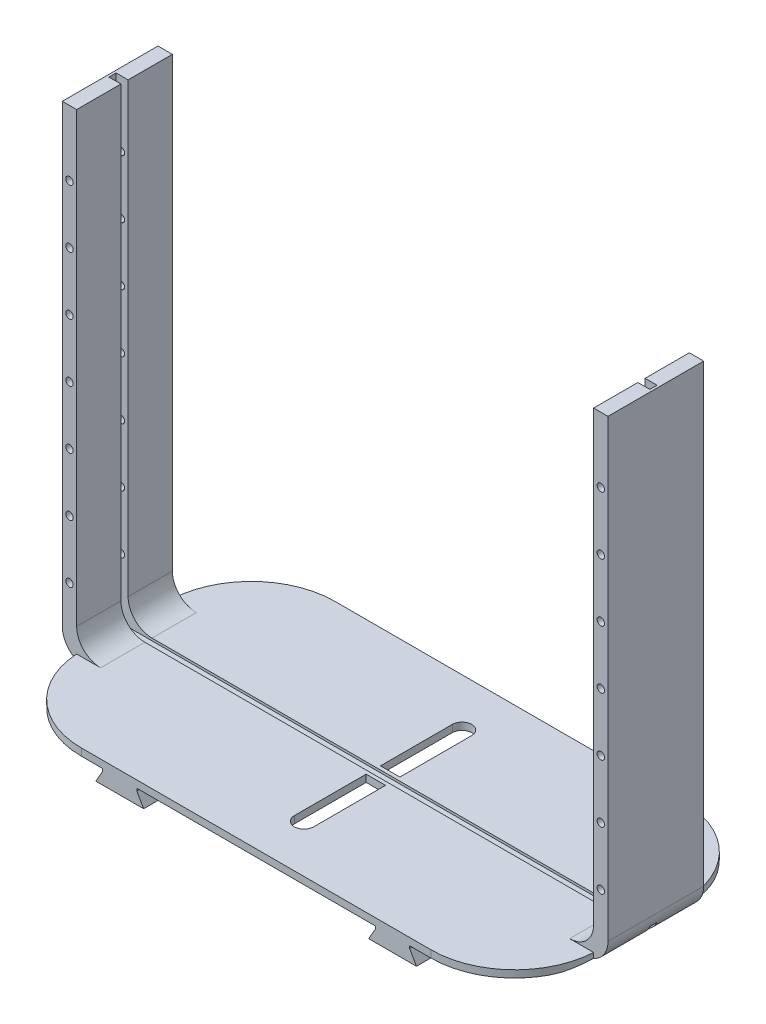
SolidWorks part; units mm, degrees
ref_plane "Front Plane" through (0, 0, 0) normal (0, 0, 1) x (1, 0, 0)
ref_plane "Top Plane" through (0, 0, 0) normal (0, 1, 0) x (1, 0, 0)
ref_plane "Right Plane" through (0, 0, 0) normal (1, 0, 0) x (0, 0, -1)
sketch "Sketch1" plane through (0, 0, 0) normal (0, 0, 1) x (1, 0, 0)
  line L0 (0, 3) -> (228, 3)
  line L1 (0, 0) -> (228, 0)
  line L2 (0, 0) -> (0, 200)
  line L3 (0, 200) -> (228, 200)
  line L4 (228, 0) -> (228, 200)
  line L5 (0, 200) -> (6, 200)
  line L6 (0, 200) -> (0, 0)
  line L7 (0, 0) -> (6, 0)
  line L8 (6, 200) -> (6, 0)
  line L9 (228, 200) -> (222, 200)
  line L10 (228, 200) -> (228, 0)
  line L11 (228, 0) -> (222, 0)
  line L12 (222, 200) -> (222, 0)
  line L13 (49.8868, 0) -> (49.8868, -1)
  line L14 (49.8868, -1) -> (47, -6)
  line L15 (47, -6) -> (67, -6)
  line L16 (67, -6) -> (64.1132, -1)
  line L17 (64.1132, -1) -> (64.1132, 0)
  line L18 (64.1132, 0) -> (49.8868, 0)
  line L19 (114, 3) -> (0, 3) construction
  line L20 (114, 200) -> (114, -47.4765) construction
  line L21 (0, 100) -> (228, 100) construction
  line L22 (57, 3) -> (57, 0) construction
  line L23 (57, -6) -> (57, 0) construction
  line L24 (163.8868, -1) -> (163.8868, 0)
  line L25 (0, 200) -> (6, 200) construction
  line L26 (0, 200) -> (6, 200) construction
  line L27 (0, 200) -> (6, 200) construction
  line L28 (3, 200) -> (3, 0) construction
  line L29 (161, -6) -> (163.8868, -1)
  line L30 (181, -6) -> (161, -6)
  line L31 (178.1132, -1) -> (181, -6)
  line L32 (178.1132, 0) -> (178.1132, -1)
  line L33 (163.8868, 0) -> (178.1132, 0)
  circle A0 centre (3, 75.75) radius 1.55
  circle A1 centre (3, 51.5) radius 1.55
  circle A2 centre (3, 27.25) radius 1.55
  circle A3 centre (3, 100) radius 1.55
  circle A4 centre (3, 172.75) radius 1.55
  circle A5 centre (3, 148.5) radius 1.55
  circle A6 centre (3, 124.25) radius 1.55
  circle A7 centre (225, 124.25) radius 1.55
  circle A8 centre (225, 148.5) radius 1.55
  circle A9 centre (225, 172.75) radius 1.55
  circle A10 centre (225, 75.75) radius 1.55
  circle A11 centre (225, 100) radius 1.55
  circle A12 centre (225, 51.5) radius 1.55
  circle A13 centre (225, 27.25) radius 1.55
  dimension "D12" = 3.1
  dimension "D13" = 3.1
  dimension "D14" = 3.1
  dimension "D15" = 3.1
  dimension "D17" = 24.25
  dimension "D1" = 3
  dimension "D2" = 228
  dimension "D3" = 6
  dimension "D4" = 6
  dimension "D5" = 200
  dimension "D6" = 60
  dimension "D7" = 60
  dimension "D8" = 20
  dimension "D9" = 1
  dimension "D10" = 1
  dimension "D11" = 6
  dimension "D16" = 24.25
  dimension "D18" = 24.25
  dimension "D19" = 24.25
extrude "Boss-Extrude1" add sketch "Sketch1" along normal blind 106 contours L3 L12 L0 L4 A12 A10 A9 A8 A7 A11 A13 | L32 L1 L24 L29 L30 L31 | L16 L17 L1 L13 L14 L15 | L12 L0 L8 L1 | L0 L12 L1 L4 | L8 L0 L2 L1 | L8 L3 L2 L0 A5 A0 A1 A2 A3 A4 A6 region at (3, 101.5702, 0) region at (3, 1.5, 0) region at (114, 1.5, 0) region at (225, 101.5702, 0) region at (225, 1.5, 0) region at (57, -3.1928, 0) region at (171, -3.1928, 0)
sketch "Sketch2" plane through (0, 200, 0) normal (0, 1, 0) x (1, 0, 0)
  line L0 (6, -106) -> (6, 0) construction
  line L1 (0, -106) -> (6, -106)
  line L2 (0, -106) -> (0, -73)
  line L3 (0, -73) -> (6, -73)
  line L4 (6, -106) -> (6, -73)
  line L5 (6, -106) -> (6, 0) construction
  line L6 (0, 0) -> (6, 0)
  line L7 (0, 0) -> (0, -33)
  line L8 (0, -33) -> (6, -33)
  line L9 (6, 0) -> (6, -33)
  line L10 (228, -106) -> (228, 0) construction
  line L11 (222, -106) -> (228, -106)
  line L12 (222, -106) -> (222, -73)
  line L13 (222, -73) -> (228, -73)
  line L14 (228, -106) -> (228, -73)
  line L15 (222, -106) -> (222, 0) construction
  line L16 (228, 0) -> (222, 0)
  line L17 (228, 0) -> (228, -33)
  line L18 (228, -33) -> (222, -33)
  line L19 (222, 0) -> (222, -33)
  line L20 (0, -53) -> (228, -53) construction
  line L21 (0, -106) -> (0, 0) construction
  line L22 (114, 0) -> (114, -106) construction
  line L23 (6, 0) -> (222, 0) construction
  line L24 (6, -106) -> (222, -106) construction
  line L25 (114, -86) -> (114, -20) construction
  line L26 (109.95, -86) -> (109.95, -20)
  line L27 (118.05, -86) -> (118.05, -20)
  line L28 (109.95, -53) -> (118.05, -53) construction
  line L29 (109.95, -56) -> (118.05, -56)
  line L30 (109.95, -56) -> (109.95, -50)
  line L31 (109.95, -50) -> (118.05, -50)
  line L32 (118.05, -56) -> (118.05, -50)
  line L34 (6, -54.5) -> (1, -54.5)
  line L35 (6, -54.5) -> (6, -51.5)
  line L36 (6, -51.5) -> (1, -51.5)
  line L37 (1, -54.5) -> (1, -51.5)
  line L42 (1, -53) -> (6, -53) construction
  line L43 (222, -51.5) -> (227, -51.5)
  line L44 (227, -54.5) -> (227, -51.5)
  line L45 (222, -54.5) -> (227, -54.5)
  line L46 (222, -54.5) -> (222, -51.5)
  line L48 (227, -54.5) -> (1, -54.5)
  line L49 (227, -54.5) -> (227, -51.5)
  line L50 (227, -51.5) -> (1, -51.5)
  line L51 (1, -54.5) -> (1, -51.5)
  arc A0 (109.95, -86) -> (118.05, -86) centre (114, -86) ccw
  arc A1 (118.05, -20) -> (109.95, -20) centre (114, -20) ccw
  point P40 (114, -53)
  point P45 (114, -15.95)
  point P46 (114, -90.05)
  point P48 (114, -53)
  line M14 (6, 0) -> (0, 0)
  line M15 (0, 0) -> (0, -106)
  line M16 (0, -106) -> (6, -106)
  line M17 (6, -106) -> (6, 0)
  dimension "D2" = 74.1
  dimension "D1" = 8.1
  dimension "D3" = 20
  dimension "D4" = 20
  dimension "D5" = 20
  dimension "D6" = 20
  dimension "D7" = 6
  dimension "D8" = 3
  dimension "D9" = 5
  dimension "D10" = 3
extrude "Cut-Extrude1" cut sketch "Sketch2" against normal blind 234 contours L27 A1 L26 L31 | L26 A0 L27 L29 | L11 L14 L13 L12 | L16 L19 L18 L17 | L8 M15 M17 M14 | L3 M15 M16 M17 region at (3, 200, 89.5) region at (3, 200, 16.5) region at (114, 200, 72.6027) region at (114, 200, 33.3973) region at (225, 200, 89.5) region at (225, 200, 16.5)
fillet "Fillet2" radius 10 4 edges at (228, 0, 53) (222, 3, 53) (0, 0, 53) (6, 3, 53)
extrude "Cut-Extrude2" cut sketch "Sketch2<5>" against normal blind 198 contours L46 L45 L44 L43 | L46 L50 L32 L48 | L30 L50 L48 M17 | L32 L50 L30 L48 | L37 L34 L36 M17 region at (3.5, 200, 53) region at (57.975, 200, 53) region at (114, 200, 53) region at (170.025, 200, 53) region at (224.5, 200, 53)
sketch "Sketch2<5>" plane through (0, 200, 0) normal (0, 1, 0) x (1, 0, 0) same geometry as "Sketch2"
fillet "Fillet1" radius 35 4 edges at (222, 1.9174, 0) (6, 1.9174, 0) (6, 1.9174, 106) (222, 1.9174, 106)
